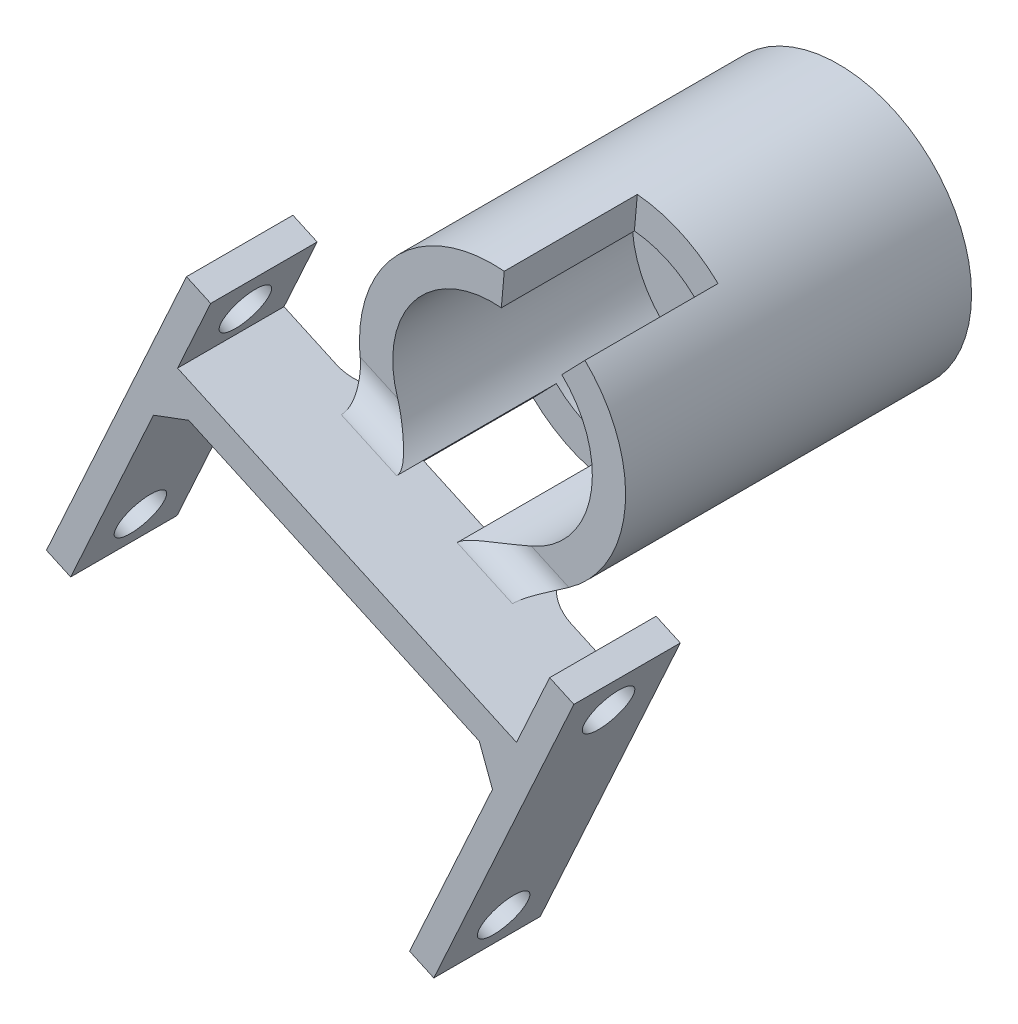
SolidWorks part; units mm, degrees
ref_plane "Front Plane" through (0, 0, 0) normal (0, 0, 1) x (1, 0, 0)
ref_plane "Top Plane" through (0, 0, 0) normal (0, 1, 0) x (1, 0, 0)
ref_plane "Right Plane" through (0, 0, 0) normal (1, 0, 0) x (0, 0, -1)
sketch "Sketch1" plane through (0, 0, 0) normal (0, 0, 1) x (1, 0, 0)
  circle A0 centre (0, 0) radius 3.285
  circle A1 centre (0, 0) radius 10
  circle A2 centre (0, 0) radius 7.5
  dimension "D1" = 6.57
  dimension "D2" = 20
  dimension "D3" = 15
extrude "Boss-Extrude1" add sketch "Sketch1" along normal blind 2 contours A2 A0 region at (-7.2879, 0, 0)
extrude "Boss-Extrude2" add sketch "Sketch1<3>" along normal blind 10 contours A1 A2 region at (-9.7172, 0, 0)
sketch "Sketch1<3>" plane through (0, 0, 0) normal (0, 0, 1) x (1, 0, 0) same geometry as "Sketch1"
sketch "Sketch2" plane through (0, 0, 10) normal (0, 0, 1) x (1, 0, 0)
  line L0 (-6.946, -7.194) -> (-5.2095, -5.3955)
  line L1 (5.2095, 5.3955) -> (6.946, 7.194)
  line L2 (0.6605, 7.4709) -> (0.8807, 9.9611)
  line L3 (-0.6605, -7.4709) -> (-0.8807, -9.9611)
  line L4 (0.6605, 7.4709) -> (5.2095, 5.3955) construction
  line L5 (-5.2095, -5.3955) -> (-0.6605, -7.4709) construction
  circle A0 centre (0, 0) radius 10 construction
  circle A1 centre (0, 0) radius 7.5 construction
  circle A2 centre (0, 0) radius 10
  circle A3 centre (0, 0) radius 7.5
  circle M1 centre (0, 0) radius 7.5
  circle M2 centre (0, 0) radius 10
  dimension "D1" = 5
  dimension "D2" = 5
extrude "Boss-Extrude3" add sketch "Sketch2" along normal blind 10 contours L2 L0 M1 M2 | L3 L1 M1 M2 region at (-8.9128, 4.0663, 10) region at (-0.5679, -8.7339, 10)
sketch "Sketch3" plane through (0, 0, 20) normal (0, 0, 1) x (1, 0, 0)
  line L0 (-5.0744, -8.0479) -> (-11.1396, -5.2807) construction
  line L2 (-0.6605, -7.4709) -> (-45490.0559, 20746.2014) construction
  line L3 (11.6216, -13.0743) -> (10.6433, -15.2187)
  line L4 (-17.4916, 0.208) -> (-18.47, -1.9364)
  line L5 (-17.4916, 0.208) -> (11.6216, -13.0743)
  line L6 (10.6433, -15.2187) -> (-18.47, -1.9364)
  dimension "D1" = 13.5
  dimension "D2" = 13.5
extrude "Boss-Extrude4" add sketch "Sketch3" along normal blind 8
fillet "Fillet1" radius 2 2 edges at (-7.2888, -4.4468, 20) (1.4188, -8.4195, 20)
fillet "Fillet2" radius 2 2 edges at (1.3419, -9.9096, 20) (-8.3638, -5.4815, 20)
sketch "Sketch4" plane through (-3.9133, -8.5776, 0) normal (-0.4151, -0.9098, 0) x (0.9098, -0.4151, 0)
  line L0 (-16, 20) -> (-7.4237, 20) construction
  line L1 (-16, 28) -> (-14, 28)
  line L2 (-16, 28) -> (-16, 20)
  line L3 (-16, 20) -> (-14, 20)
  line L4 (-14, 28) -> (-14, 20)
  line L5 (-16, 28) -> (16, 28) construction
  line L6 (16, 20) -> (14, 20)
  line L7 (16, 20) -> (16, 28)
  line L8 (16, 28) -> (14, 28)
  line L9 (14, 20) -> (14, 28)
  dimension "D1" = 2
  dimension "D2" = 2
extrude "Boss-Extrude5" add sketch "Sketch4" along normal blind 17
chamfer "Chamfer1" distance 2 angle 45 2 edges at (-16.6504, -2.7665, 24) (8.8237, -14.3886, 24)
sketch "Sketch6" plane through (-14.5566, 6.6412, 0) normal (-0.9098, 0.4151, 0) x (0, 0, 1)
  line L0 (28, -26.4281) -> (20, -26.4281) construction
  line L1 (20, -7.0711) -> (20, -26.4281) construction
  circle A0 centre (24, -23.4281) radius 1.825
  dimension "D1" = 3.65
  dimension "D2" = 3
  dimension "D3" = 4
extrude "Cut-Extrude1" cut sketch "Sketch6" against normal up to surface (32 mm away) up to face at (7.6043, -21.8797, 24)
sketch "Sketch7" plane through (-2.935, -6.4332, 0) normal (0.4151, 0.9098, 0) x (0.9098, -0.4151, 0)
  line L0 (16, -20) -> (9.6954, -20) construction
  line L1 (16, -28) -> (14, -28)
  line L2 (16, -28) -> (16, -20)
  line L3 (16, -20) -> (14, -20)
  line L4 (14, -28) -> (14, -20)
  line L5 (-9.6954, -20) -> (-16, -20) construction
  line L6 (-16, -28) -> (-14, -28)
  line L7 (-16, -28) -> (-16, -20)
  line L8 (-16, -20) -> (-14, -20)
  line L9 (-14, -28) -> (-14, -20)
  dimension "D1" = 2
  dimension "D2" = 2
extrude "Boss-Extrude6" add sketch "Sketch7" along normal blind 6
sketch "Sketch8" plane through (-14.5566, 6.6412, 0) normal (-0.9098, 0.4151, 0) x (0, 0, 1)
  line L0 (24, -1.0711) -> (24, -26.4281) construction
  line L1 (20, -1.0711) -> (28, -1.0711) construction
  line L2 (28, -26.4281) -> (20, -26.4281) construction
  circle A0 centre (24, -4.4281) radius 1.825
  circle A3 centre (24, -23.4281) radius 1.825 construction
  dimension "D2" = 3.65
  dimension "D1" = 19
extrude "Cut-Extrude2" cut sketch "Sketch8" against normal up to surface (32 mm away) up to face at (4.0747, -29.6161, 24)
sketch "Sketch9" plane through (0, 0, 0) normal (0, 0, -1) x (-1, 0, 0)
  circle A0 centre (0, 0) radius 10
  circle A1 centre (0, 0) radius 5
  dimension "D1" = 10
extrude "Boss-Extrude7" add sketch "Sketch9" along normal blind 6
